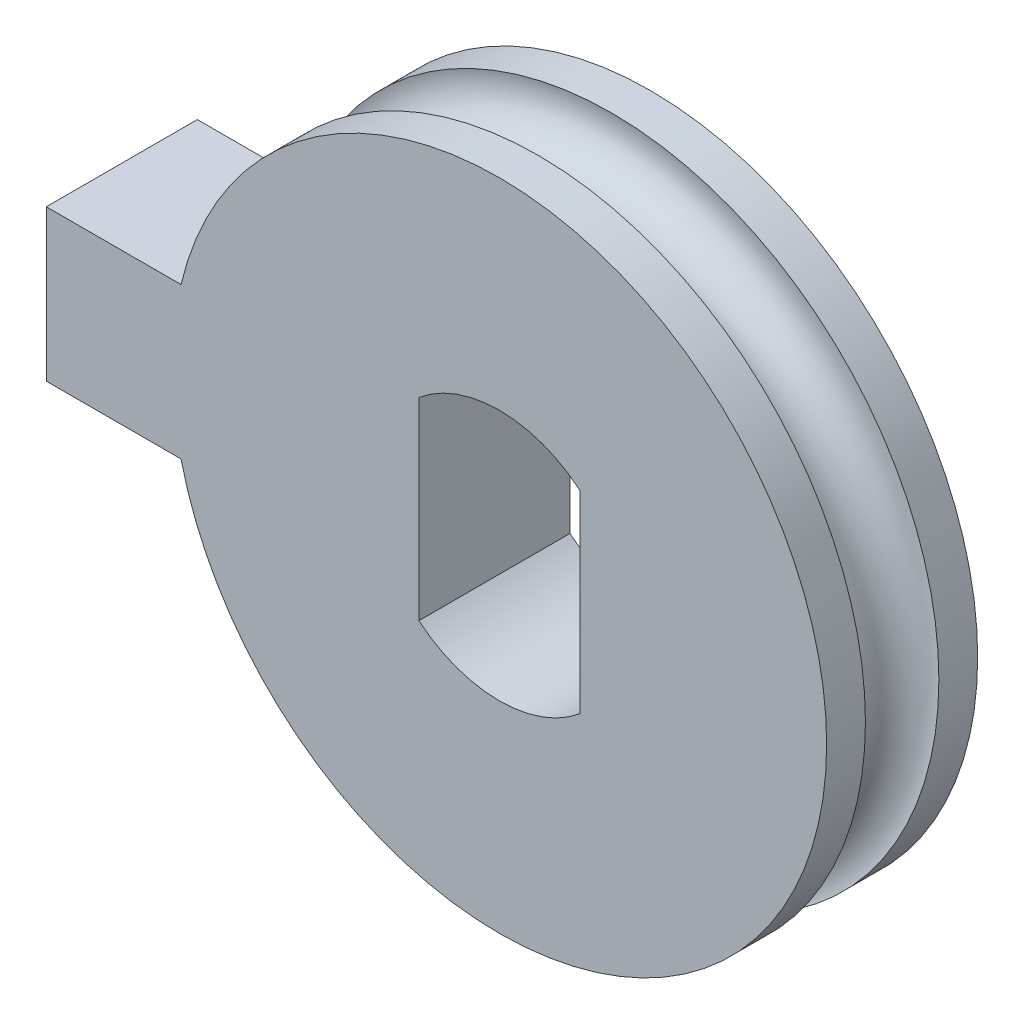
SolidWorks part; units mm, degrees
ref_plane "Спереди" through (0, 0, 0) normal (0, 0, 1) x (1, 0, 0)
ref_plane "Сверху" through (0, 0, 0) normal (0, 1, 0) x (1, 0, 0)
ref_plane "Справа" through (0, 0, 0) normal (1, 0, 0) x (0, 0, -1)
other "Configuration Table"
sketch "Эскиз1" plane through (0, 0, 0) normal (0, 0, 1) x (1, 0, 0)
  line L0 (-1.6, -1.9205) -> (-1.6, 1.9205) construction
  line L1 (-1.6, 0) -> (-1.6, 1.9205)
  line L2 (-1.6, 0) -> (-1.6, -1.9205)
  line L3 (1.6, -1.9205) -> (1.6, 1.9205)
  line L4 (-6.3246, 1.5) -> (-1.6, 1.5) construction
  line L5 (-9, 1.5) -> (-6.3246, 1.5)
  line L6 (-9, 1.5) -> (-9, -1.5)
  line L7 (-9, -1.5) -> (-6.3246, -1.5)
  line L10 (-6.3246, -1.5) -> (-1.6, -1.5) construction
  arc A0 (-6.3246, -1.5) -> (-6.3246, 1.5) centre (0, 0) ccw
  arc A1 (-1.6, -1.9205) -> (1.6, -1.9205) centre (0, 0) ccw
  arc A2 (1.6, 1.9205) -> (-1.6, 1.9205) centre (0, 0) ccw
  arc A3 (-6.3246, 1.5) -> (-6.3246, -1.5) centre (0, 0) ccw construction
  point P6 (0, 0)
  point P12 (1.6, 0)
  point P16 (-6.3246, 1.5)
  point P17 (-6.3246, -1.5)
  dimension "D4" = 6.5
  dimension "D5" = 9
  dimension "D6" = 1.5
  dimension "D7" = 1.5
  dimension "D8" = 3.2
extrude "Бобышка-Вытянуть1" add sketch "Эскиз1" along normal blind 3
sketch "Эскиз1<2>" plane through (0, 0, 0) normal (0, 0, 1) x (1, 0, 0) same geometry as "Эскиз1"
ref_plane "Плоскость1" through (0, 0, 0) normal (0, -1, 0) x (-1, 0, 0)
sketch "Эскиз4" plane through (0, 0, 0) normal (0, -1, 0) x (-1, 0, 0)
  line L0 (6.3246, 0) -> (6.3246, -1.5) construction
  line L1 (6.3246, -3) -> (6.3246, 0) construction
  line L2 (6.3246, -1.5) -> (6.3246, -3) construction
  line L3 (0, 0) -> (0, 5.504) construction
  circle A0 centre (6.3246, -1.5) radius 0.75
revolve "Вырез-Повернуть1" cut sketch "Эскиз4" angle 360 about L3
